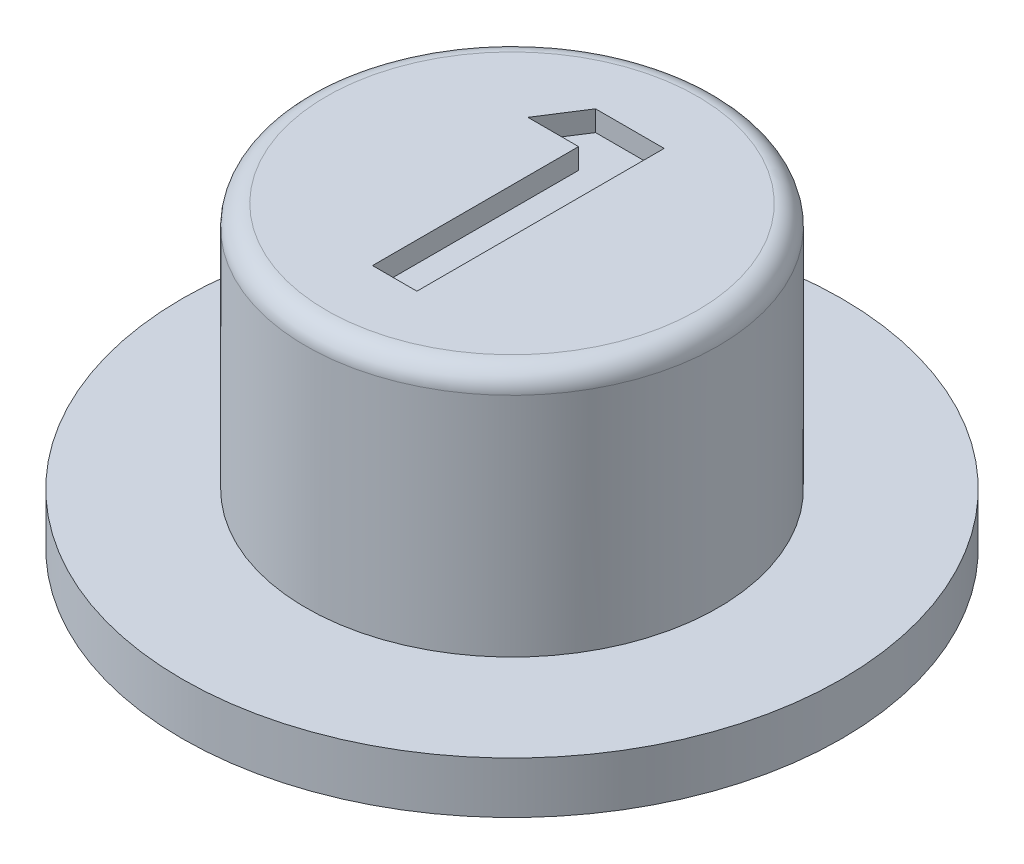
SolidWorks part; units mm, degrees
ref_plane "Front Plane" through (0, 0, 0) normal (0, 0, 1) x (1, 0, 0)
ref_plane "Top Plane" through (0, 0, 0) normal (0, 1, 0) x (1, 0, 0)
ref_plane "Right Plane" through (0, 0, 0) normal (1, 0, 0) x (0, 0, -1)
sketch "Sketch1" plane through (0, 0, 0) normal (0, 0, 1) x (1, 0, 0)
  line L1 (0, 7.25) -> (5, 7.25)
  line L2 (5, 7.25) -> (5, 1.25)
  line L3 (5, 1.25) -> (8, 1.25)
  line L4 (8, 1.25) -> (8, 0)
  line L6 (0, 7.25) -> (0, 6.9292) construction
  line L7 (0, 7.25) -> (0, 0)
  line L10 (0, 0) -> (8, 0)
  dimension "D1" = 5
  dimension "D2" = 3
  dimension "D3" = 6
  dimension "D4" = 1.25
revolve "Revolve1" add sketch "Sketch1" angle 360 about L6
sketch "Sketch2" plane through (0, 0, 0) normal (0, -1, 0) x (1, 0, 0)
  line L1 (-1.75, -1.25) -> (1.75, -1.25)
  line L2 (-1.75, -1.25) -> (-1.75, 1.25)
  line L3 (-1.75, 1.25) -> (1.75, 1.25)
  line L4 (1.75, -1.25) -> (1.75, 1.25)
  line L5 (-1.75, -1.25) -> (1.75, 1.25) construction
  line L6 (-1.75, 1.25) -> (1.75, -1.25) construction
  point P0 (0, 0)
  dimension "D1" = 3.5
  dimension "D2" = 2.5
extrude "Cut-Extrude1" cut sketch "Sketch2" against normal blind 3.5 contours L3 L4 L1 L2
fillet "Fillet1" radius 0.5 1 edges at (-5, 7.25, 0)
sketch "Sketch3" plane through (0, 7.25, 0) normal (0, 1, 0) x (1, 0, 0)
  line L0 (-3.3541, -3) -> (3.3541, -3) construction
  line L1 (0, 0) -> (0, -3) construction
  circle A0 centre (0, 0) radius 4.5 construction
  text T0 "1" font "Century Gothic" height 6
  dimension "D1" = 3
extrude "Cut-Extrude2" cut sketch "Sketch3" against normal blind 0.5
